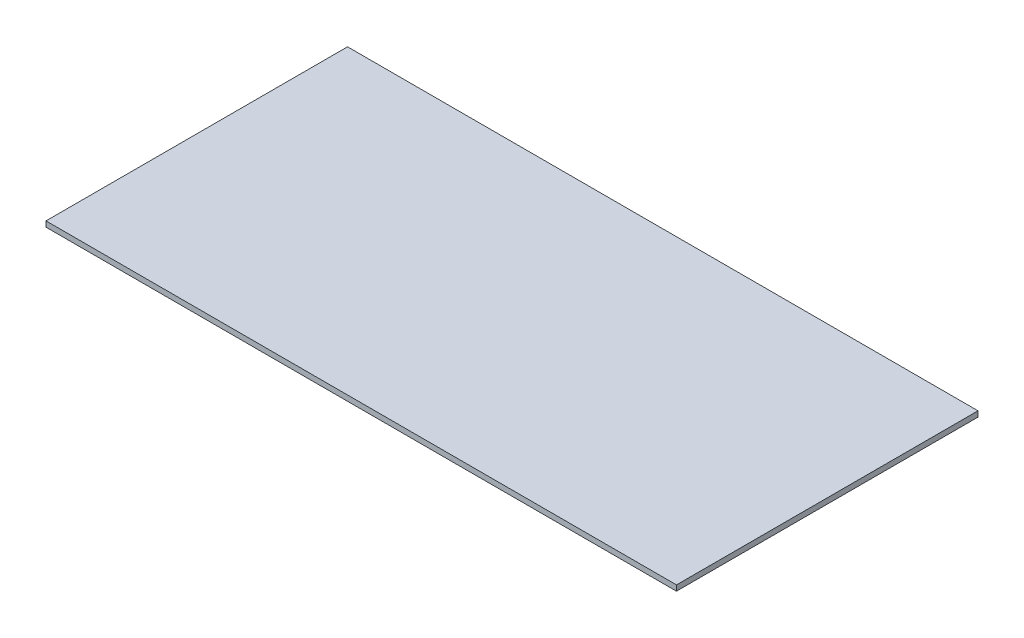
SolidWorks part; units mm, degrees
material "PC High Viscosity"
ref_plane "Front Plane" through (0, 0, 0) normal (0, 0, 1) x (1, 0, 0)
ref_plane "Top Plane" through (0, 0, 0) normal (0, 1, 0) x (1, 0, 0)
ref_plane "Right Plane" through (0, 0, 0) normal (1, 0, 0) x (0, 0, -1)
sketch "Sketch1" plane through (0, 0, 0) normal (0, 1, 0) x (1, 0, 0)
  line L1 (0, 0) -> (584.2, 0)
  line L2 (0, 0) -> (0, 279.4)
  line L3 (0, 279.4) -> (584.2, 279.4)
  line L4 (584.2, 0) -> (584.2, 279.4)
  dimension "D1" = 584.2
  dimension "D2" = 279.4
extrude "Boss-Extrude1" add sketch "Sketch1" along normal blind 5.08
sketch "Sketch2" plane through (0, 5.08, 0) normal (0, 1, 0) x (1, 0, 0)
  line L0 (0, 0) -> (584.2, 0) construction
  line L1 (0, 279.4) -> (0, 0) construction
  line L2 (584.2, 0) -> (584.2, 279.4) construction
  line L3 (-57.96, 139.7) -> (662.3834, 139.7) construction
  line L4 (584.2, 279.4) -> (0, 279.4) construction
  circle A0 centre (12.7, 12.7) radius 2.032
  circle A1 centre (82.55, 12.7) radius 2.032
  circle A2 centre (152.4, 12.7) radius 2.032
  circle A3 centre (222.25, 12.7) radius 2.032
  circle A4 centre (292.1, 12.7) radius 2.032
  circle A5 centre (361.95, 12.7) radius 2.032
  circle A6 centre (431.8, 12.7) radius 2.032
  circle A7 centre (501.65, 12.7) radius 2.032
  circle A8 centre (571.5, 12.7) radius 2.032
  circle A10 centre (501.65, 266.7) radius 2.032
  circle A11 centre (431.8, 266.7) radius 2.032
  circle A12 centre (361.95, 266.7) radius 2.032
  circle A13 centre (292.1, 266.7) radius 2.032
  circle A14 centre (222.25, 266.7) radius 2.032
  circle A15 centre (152.4, 266.7) radius 2.032
  circle A16 centre (82.55, 266.7) radius 2.032
  circle A17 centre (571.5, 76.2) radius 2.032
  circle A18 centre (571.5, 139.7) radius 2.032
  circle A19 centre (571.5, 203.2) radius 2.032
  circle A20 centre (571.5, 266.7) radius 2.032
  dimension "D1" = 4.064
  dimension "D2" = 12.7
  dimension "D3" = 12.7
  dimension "D5" = 12.7
  dimension "D6" = 139.7
  dimension "D8" = 12.7
  dimension "D4" = 9
  dimension "D7" = 5
